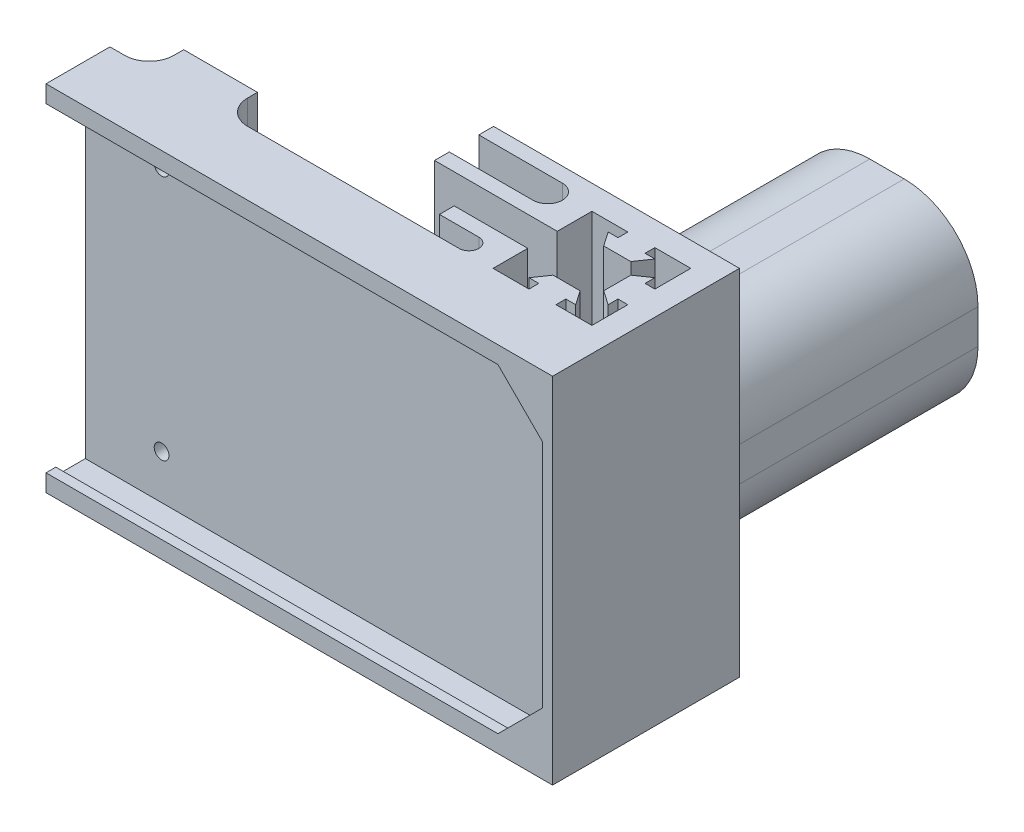
SolidWorks part; units mm, degrees
ref_plane "Front Plane" through (0, 0, 0) normal (0, 0, 1) x (1, 0, 0)
ref_plane "Top Plane" through (0, 0, 0) normal (0, 1, 0) x (1, 0, 0)
ref_plane "Right Plane" through (0, 0, 0) normal (1, 0, 0) x (0, 0, -1)
sketch "Sketch5" plane through (0, 0, 0) normal (0, 1, 0) x (1, 0, 0)
  line L1 (0, 0) -> (30, 0)
  line L2 (0, 0) -> (0, -30)
  line L3 (0, -30) -> (30, -30)
  line L4 (30, 0) -> (30, -30)
  dimension "D1" = 30
  dimension "D2" = 30
extrude "Boss-Extrude3" add sketch "Sketch5" along normal blind 72 contours L1 L4 L3 L2
sketch "Sketch6" plane through (0, 72, 0) normal (0, 1, 0) x (1, 0, 0)
  line L0 (0, 0) -> (0, -30) construction
  line L1 (4.95, -4.95) -> (25.05, -4.95)
  line L2 (4.95, -4.95) -> (4.95, -25.05)
  line L3 (4.95, -25.05) -> (25.05, -25.05)
  line L4 (25.05, -4.95) -> (25.05, -25.05)
  line L5 (0, -30) -> (30, -30) construction
  line L6 (12.25, -4.95) -> (12.25, -6.95)
  line L7 (12.25, -6.95) -> (10.25, -6.95)
  line L8 (17.75, -4.95) -> (17.75, -6.95)
  line L9 (17.75, -6.95) -> (19.75, -6.95)
  line L10 (4.95, -15) -> (25.05, -15) construction
  line L11 (10.25, -6.95) -> (12.25, -9.85)
  line L12 (19.75, -6.95) -> (17.75, -9.85)
  line L13 (12.25, -9.85) -> (17.75, -9.85)
  line L14 (19.75, -23.05) -> (17.75, -20.15)
  line L15 (17.75, -23.05) -> (19.75, -23.05)
  line L16 (17.75, -25.05) -> (17.75, -23.05)
  line L17 (12.25, -25.05) -> (12.25, -23.05)
  line L18 (12.25, -23.05) -> (10.25, -23.05)
  line L19 (10.25, -23.05) -> (12.25, -20.15)
  line L20 (12.25, -20.15) -> (17.75, -20.15)
  line L21 (25.05, -12.25) -> (23.05, -12.25)
  line L22 (23.05, -12.25) -> (23.05, -10.25)
  line L23 (23.05, -10.25) -> (20.15, -12.25)
  line L24 (20.15, -12.25) -> (20.15, -17.75)
  line L25 (23.05, -19.75) -> (20.15, -17.75)
  line L26 (23.05, -17.75) -> (23.05, -19.75)
  line L27 (25.05, -17.75) -> (23.05, -17.75)
  point P32 (20.15, -15)
  dimension "D1" = 20.1
  dimension "D2" = 20.1
  dimension "D3" = 4.95
  dimension "D4" = 4.95
  dimension "D5" = 2
  dimension "D6" = 7.3
  dimension "D7" = 2
  dimension "D8" = 7.3
  dimension "D9" = 2
  dimension "D10" = 2
  dimension "D11" = 2
  dimension "D12" = 7.3
  dimension "D13" = 2
  dimension "D14" = 2.9
  dimension "D15" = 2
  dimension "D16" = 2
  dimension "D17" = 2.9
  dimension "D18" = 2
extrude "Cut-Extrude1" cut sketch "Sketch6" against normal through all contours L2 L10 L24 L23 L22 L21 L4 L1 L8 L9 L12 L13 L11 L7 L6 | L10 L2 L3 L17 L18 L19 L20 L14 L15 L16 L4 L27 L26 L25 L24 region at (14.1958, 72, 10.1548) region at (14.1958, 72, 19.8452)
sketch "Sketch8" plane through (0, 72, 0) normal (0, 1, 0) x (1, 0, 0)
  line L0 (4.95, -4.95) -> (4.95, -25.05) construction
  line L1 (4.95, -12) -> (0, -12)
  line L2 (4.95, -12) -> (4.95, -18)
  line L3 (4.95, -18) -> (0, -18)
  line L4 (0, -12) -> (0, -18)
  line L5 (0, 0) -> (0, -30) construction
  line L6 (0, 0) -> (30, 0) construction
  dimension "D1" = 6
  dimension "D2" = 12
extrude "Cut-Extrude3" cut sketch "Sketch8" against normal through all contours L4 L3 L2 L1
sketch "Sketch10" plane through (0, 0, 0) normal (-1, 0, 0) x (0, 0, 1)
  line L0 (0, 0) -> (12, 0) construction
  line L10 (0, 0) -> (12, 0) construction
  line L11 (0, 72) -> (3, 72)
  line L12 (0, 72) -> (0, 0)
  line L13 (0, 0) -> (3, 0)
  line L14 (3, 72) -> (3, 0)
  line L15 (9, 0) -> (12, 0)
  line L16 (9, 0) -> (9, 72)
  line L17 (9, 72) -> (12, 72)
  line L18 (12, 0) -> (12, 72)
  line L19 (0, 72) -> (12, 72) construction
  line L21 (18, 0) -> (21, 0)
  line L22 (18, 0) -> (18, 72)
  line L23 (18, 72) -> (21, 72)
  line L24 (21, 0) -> (21, 72)
  dimension "D1" = 3
  dimension "D2" = 3
  dimension "D3" = 3
  dimension "D4" = 6
  dimension "D5" = 6
extrude "Boss-Extrude4" add sketch "Sketch10" along normal blind 10
sketch "Sketch11" plane through (0, 0, 0) normal (0, 0, -1) x (-1, 0, 0)
  line L0 (10, 72) -> (10, 0) construction
  line L5 (-28.5, 54.5) -> (8.5, 54.5)
  line L6 (-28.5, 54.5) -> (-28.5, 17.5)
  line L7 (-28.5, 17.5) -> (8.5, 17.5)
  line L8 (8.5, 54.5) -> (8.5, 17.5)
  line L9 (10, 72) -> (-30, 72) construction
  line L10 (-30, 72) -> (-30, 0) construction
  dimension "D1" = 17.5
  dimension "D2" = 1.5
  dimension "D3" = 17.5
  dimension "D4" = 1.5
extrude "Boss-Extrude5" add sketch "Sketch11" along normal blind 50 contours L7 L8 L5 L6
sketch "Sketch14" plane through (0, 0, -50) normal (0, 0, -1) x (-1, 0, 0)
  line L0 (-10, 17.5) -> (-10, 54.5) construction
  line L2 (-28.5, 17.5) -> (8.5, 17.5) construction
  line L3 (-28.5, 54.5) -> (8.5, 54.5) construction
  circle A0 centre (-10, 36) radius 13.5 construction
  circle A1 centre (-10, 49.5) radius 1.5
  circle A2 centre (1.6913, 29.25) radius 1.5
  circle A3 centre (-21.6913, 29.25) radius 1.5
  point P15 (-10, 36)
  dimension "D1" = 27
  dimension "D2" = 3
  dimension "D3" = 3
  dimension "D4" = 20.25
  dimension "D5" = 11.6913
extrude "Cut-Extrude4" cut sketch "Sketch14" against normal blind 20
fillet "Fillet2" radius 15 4 edges at (-8.5, 17.5, -25) (-8.5, 54.5, -25) (28.5, 54.5, -25) (28.5, 17.5, -25)
sketch "Sketch16" plane through (0, 0, 0) normal (-1, 0, 0) x (0, 0, 1)
  line L0 (21, 0) -> (30, 0) construction
  line L1 (30, 72) -> (25, 72)
  line L2 (30, 72) -> (30, 0)
  line L3 (30, 0) -> (25, 0)
  line L4 (25, 72) -> (25, 0)
  dimension "D1" = 5
extrude "Boss-Extrude6" add sketch "Sketch16" along normal blind 73
sketch "Sketch19" plane through (0, 0, 30) normal (0, 0, 1) x (1, 0, 0)
  line L0 (-73, 72) -> (-73, 70)
  line L1 (-73, 0) -> (-73, 72) construction
  line L2 (-73, 70) -> (17.3934, 70)
  line L3 (28, 59.3934) -> (28, 12.6066)
  line L4 (17.3934, 2) -> (-73, 2)
  line L5 (-73, 2) -> (-73, 0)
  line L6 (-73, 0) -> (30, 0)
  line L7 (30, 0) -> (30, 72)
  line L8 (30, 72) -> (30, 0) construction
  line L9 (30, 72) -> (-73, 72)
  line L10 (17.3934, 70) -> (28, 59.3934)
  line L11 (17.3934, 2) -> (28, 12.6066)
  dimension "D1" = 2
  dimension "D2" = 2
  dimension "D3" = 2
  dimension "D4" = 15
  dimension "D5" = 135
  dimension "D6" = 135
  dimension "D7" = 15
extrude "Boss-Extrude7" add sketch "Sketch19" along normal blind 8
sketch "Sketch20" plane through (0, 70, 0) normal (0, -1, 0) x (1, 0, 0)
  line L0 (30, 0) -> (30, 38) construction
  line L1 (-73, 38) -> (30, 38)
  line L2 (-73, 38) -> (-73, 36)
  line L3 (-73, 36) -> (30, 36)
  line L4 (30, 38) -> (30, 36)
  dimension "D1" = 2
extrude "Boss-Extrude8" add sketch "Sketch20" along normal blind 1.5
sketch "Sketch21" plane through (0, 2, 0) normal (0, 1, 0) x (1, 0, 0)
  line L0 (30, 0) -> (30, -38) construction
  line L1 (-73, -38) -> (30, -38)
  line L2 (-73, -38) -> (-73, -36)
  line L3 (-73, -36) -> (30, -36)
  line L4 (30, -38) -> (30, -36)
  dimension "D1" = 2
extrude "Boss-Extrude9" add sketch "Sketch21" along normal blind 1.5
sketch "Sketch22" plane through (0, 72, 0) normal (0, 1, 0) x (1, 0, 0)
  line L0 (-73, -25) -> (0, -25) construction
  line L3 (-65, -25) -> (-50, -25)
  line L4 (-65, -25) -> (-65, -18)
  line L5 (-65, -18) -> (-50, -18)
  line L6 (-50, -25) -> (-50, -18)
  dimension "D1" = 7
  dimension "D2" = 15
  dimension "D3" = 50
extrude "Boss-Extrude10" add sketch "Sketch22" against normal blind 72
fillet "Fillet4" radius 5 2 edges at (-50, 36, 25) (-65, 36, 25)
fillet "Fillet5" 2 edges at (0, 36, 3) (0, 36, 9) type full round first side face at (-5, 36, 3) second side face at (-5, 36, 9) middle face at (0, 36, 6)
fillet "Fillet6" 2 edges at (0, 36, 21) (0, 36, 25) type full round first side face at (-5, 36, 21) second side face at (-22.5, 36, 25) middle face at (0, 36, 23)
sketch "Sketch23" plane through (0, 0, 18) normal (0, 0, -1) x (-1, 0, 0)
  line L0 (57.5, 72) -> (57.5, 11) construction
  line L1 (50, 72) -> (65, 72) construction
  circle A0 centre (57.5, 61) radius 1.5
  circle A1 centre (57.5, 11) radius 1.5
  dimension "D1" = 3
  dimension "D2" = 3
  dimension "D3" = 50
  dimension "D4" = 11
extrude "Cut-Extrude5" cut sketch "Sketch23" against normal through all
sketch "Sketch24" plane through (-10, 0, 0) normal (-1, 0, 0) x (0, 0, 1)
  line L0 (0, 72) -> (0, 0) construction
  line L1 (0, 72) -> (3, 72)
  line L2 (0, 72) -> (0, 0)
  line L3 (0, 0) -> (3, 0)
  line L4 (3, 72) -> (3, 0)
  line L6 (9, 72) -> (12, 72)
  line L7 (9, 72) -> (9, 0)
  line L8 (9, 0) -> (12, 0)
  line L9 (12, 72) -> (12, 0)
  dimension "D1" = 72
extrude "Boss-Extrude11" add sketch "Sketch24" along normal blind 10
